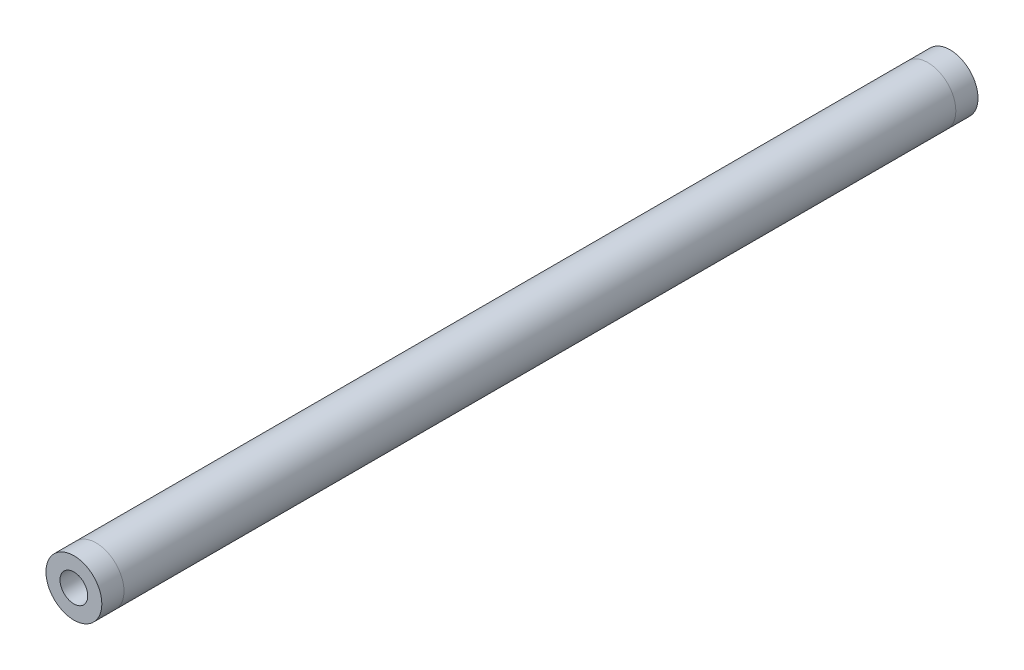
SolidWorks part; units mm, degrees
ref_plane "Front Plane" through (0, 0, 0) normal (0, 0, 1) x (1, 0, 0)
ref_plane "Top Plane" through (0, 0, 0) normal (0, 1, 0) x (1, 0, 0)
ref_plane "Right Plane" through (0, 0, 0) normal (1, 0, 0) x (0, 0, -1)
sketch "Axis" plane through (0, 0, 0) normal (1, 0, 0) x (0, 0, -1)
  line L0 (0, 0) -> (250.9439, 0) construction
  line L1 (250.9439, 0) -> (244.5939, 0)
  line L2 (250.9439, 0) -> (285.8689, 0) construction
  line L3 (0, 0) -> (-34.925, 0) construction
  point P4 (0, 0)
  point P5 (250.9439, 0)
  point P6 (244.5939, 0)
  dimension "D1" = 6.35
  dimension "D2" = 34.925
  dimension "D3" = 34.925
sketch "Sketch1" plane through (0, 0, 0) normal (0, 0, 1) x (1, 0, 0)
  circle A0 centre (0, 0) radius 8.001
  circle A1 centre (0, 0) radius 6.477
  circle A2 centre (0, 0) radius 3.9688
  dimension "D1" = 16.002
  dimension "D2" = 1.524
  dimension "D3" = 7.9375
extrude "Threaded insert 1-1" add sketch "Sketch1" against normal blind 6.35 contours A0 A1 | A1 A2 region at (-7.7747, 0, 0) region at (-6.2938, 0, 0)
extrude "Threaded insert 1-2" add sketch "Sketch1<3>" against normal blind 9.525 from surface contours A1 A2 region at (-6.2938, 0, 0) starting at face at (8.001, 0, -6.35)
sketch "Sketch1<3>" plane through (0, 0, 0) normal (0, 0, 1) x (1, 0, 0) same geometry as "Sketch1"
extrude "Tube extrude" add sketch "Sketch1<4>" against normal up to vertex (244.5939 mm away) from surface separate body contours A0 A1 region at (-7.7747, 0, 0) up to point (0, 0, -244.5939) starting at face at (6.477, 0, -6.35)
sketch "Sketch1<4>" plane through (0, 0, 0) normal (0, 0, 1) x (1, 0, 0) same geometry as "Sketch1"
extrude "Threaded insert 2-1" add sketch "Sketch1<6>" along normal blind 9.525 from surface separate body contours A1 A2 region at (-6.2938, 0, 0) starting at face at (6.477, 0, -244.5939)
sketch "Sketch1<6>" plane through (0, 0, 0) normal (0, 0, 1) x (1, 0, 0) same geometry as "Sketch1"
extrude "Threaded insert 2-2" add sketch "Sketch1<9>" against normal blind 6.35 from surface separate body contours A1 A2 | A0 A1 region at (-7.7747, 0, 0) region at (-6.2938, 0, 0) starting at face at (6.477, 0, -244.5939)
sketch "Sketch1<9>" plane through (0, 0, 0) normal (0, 0, 1) x (1, 0, 0) same geometry as "Sketch1"
combine bodies "Combine1" operation type add bodies to combine 106 104
equation "\"Threaded insert outer thickness\"= .25"
equation "\"D1@Threaded insert 1-1\"=\"Threaded insert outer thickness\""
equation "\"D1@Threaded insert 2-2\"=\"Threaded insert outer thickness\""
equation "\"D1@Axis\" = \"Threaded insert outer thickness\""
